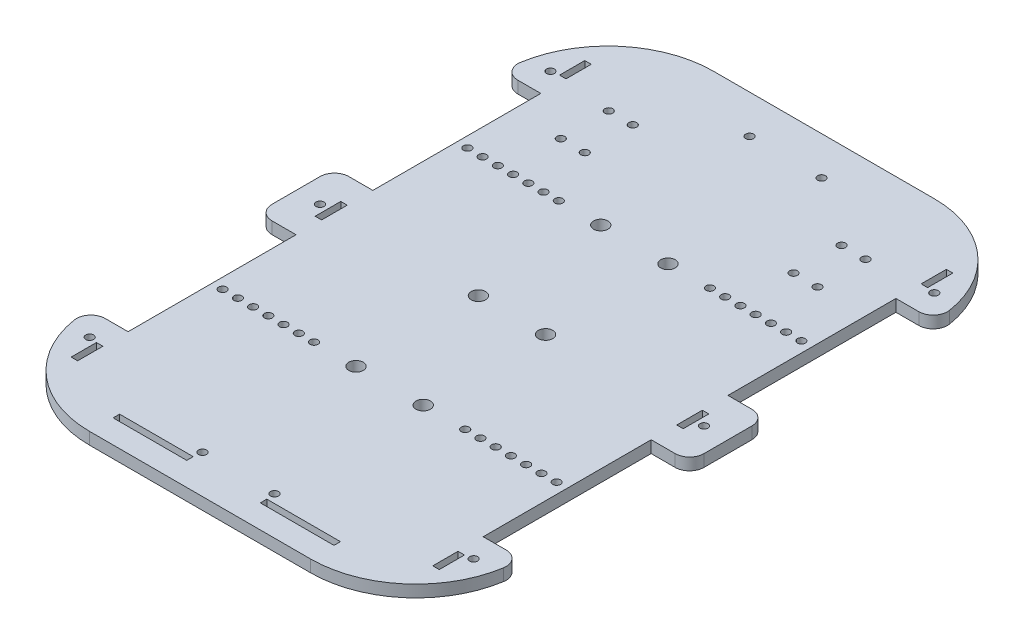
SolidWorks part; units mm, degrees
ref_plane "Ön Düzlem" through (0, 0, 0) normal (0, 0, 1) x (1, 0, 0)
ref_plane "Üst Düzlem" through (0, 0, 0) normal (0, 1, 0) x (1, 0, 0)
ref_plane "Sağ Düzlem" through (0, 0, 0) normal (1, 0, 0) x (0, 0, -1)
sketch "Sketch2" plane through (0, 0, 0) normal (0, 1, 0) x (1, 0, 0)
  line L0 (-74, -86) -> (-74, -51) construction
  line L1 (46, -130) -> (-46, -130)
  line L2 (90, -10) -> (90, 10)
  line L3 (46, 130) -> (-46, 130)
  line L4 (-90, -10) -> (-90, 10)
  line L5 (90, -130) -> (-90, 130) construction
  line L6 (90, 130) -> (-90, -130) construction
  line L7 (-83.5233, 86) -> (-74, 86)
  line L9 (-84, 16) -> (-74, 16)
  line L10 (-74, 86) -> (-74, 16)
  line L11 (-83.5233, -86) -> (-74, -86)
  line L13 (-84, -16) -> (-74, -16)
  line L14 (-74, -86) -> (-74, -16)
  line L15 (83.5233, 86) -> (74, 86)
  line L17 (84, 16) -> (74, 16)
  line L18 (74, 86) -> (74, 16)
  line L19 (83.5233, -86) -> (74, -86)
  line L21 (84, -16) -> (74, -16)
  line L22 (74, -86) -> (74, -16)
  line L23 (-74, 51) -> (74, 51) construction
  line L24 (-74, -51) -> (74, -51) construction
  line L26 (-74, 96.51) -> (-76.7, 96.51)
  line L27 (-76.7, 96.51) -> (-76.7, 107.02)
  line L28 (-74, 107.02) -> (-76.7, 107.02)
  line L29 (-74, 96.51) -> (-74, 107.02)
  line L30 (74, 96.51) -> (74, 107.02)
  line L31 (74, 107.02) -> (76.7, 107.02)
  line L32 (76.7, 96.51) -> (76.7, 107.02)
  line L33 (74, 96.51) -> (76.7, 96.51)
  line L34 (74, -107.02) -> (76.7, -107.02)
  line L35 (76.7, -96.51) -> (76.7, -107.02)
  line L36 (74, -96.51) -> (74, -107.02)
  line L37 (74, -96.51) -> (76.7, -96.51)
  line L38 (-74, -96.51) -> (-74, -107.02)
  line L39 (-74, -107.02) -> (-76.7, -107.02)
  line L40 (-76.7, -96.51) -> (-76.7, -107.02)
  line L41 (-74, -96.51) -> (-76.7, -96.51)
  line L42 (-74, 5.3333) -> (-74, -5.3333)
  line L43 (74, 5.3333) -> (74, -5.3333)
  line L44 (-74, 5.3333) -> (-76.7, 5.3333)
  line L45 (-76.7, 5.3333) -> (-76.7, -5.3333)
  line L46 (-76.7, -5.3333) -> (-74, -5.3333)
  line L47 (74, 5.3333) -> (76.7, 5.3333)
  line L48 (76.7, 5.3333) -> (76.7, -5.3333)
  line L49 (76.7, -5.3333) -> (74, -5.3333)
  line L53 (-46.02, -117.52) -> (-15.34, -117.52)
  line L55 (15.34, -117.52) -> (46.02, -117.52)
  line L56 (-46.02, -117.52) -> (-46.02, -120.22)
  line L57 (-46.02, -120.22) -> (-15.34, -120.22)
  line L58 (46.02, -120.22) -> (46.02, -117.52)
  line L59 (15.34, -117.52) -> (15.34, -120.22)
  line L60 (-15.34, -117.52) -> (-15.34, -120.22)
  line L61 (15.34, -120.22) -> (46.02, -120.22)
  arc A2 (-46, -130) -> (-89.4481, -92.9474) centre (-46, -86) cw
  arc A3 (-89.4481, 92.9474) -> (-46, 130) centre (-46, 86) cw
  arc A4 (89.4481, 92.9474) -> (46, 130) centre (46, 86) ccw
  arc A5 (89.4481, -92.9474) -> (46, -130) centre (46, -86) cw
  arc A6 (-84, 16) -> (-90, 10) centre (-84, 10) ccw
  arc A7 (-84, -16) -> (-90, -10) centre (-84, -10) cw
  arc A8 (90, 10) -> (84, 16) centre (84, 10) ccw
  arc A9 (90, -10) -> (84, -16) centre (84, -10) cw
  arc A10 (-89.4481, -92.9474) -> (-83.5233, -86) centre (-83.5233, -92) cw
  arc A11 (83.5233, -86) -> (89.4481, -92.9474) centre (83.5233, -92) cw
  arc A12 (-89.4481, 92.9474) -> (-83.5233, 86) centre (-83.5233, 92) ccw
  arc A13 (89.4481, 92.9474) -> (83.5233, 86) centre (83.5233, 92) cw
  point P0 (0, 0)
  point P34 (-90, -16)
  point P39 (90, -16)
  point P46 (-90, 86)
  point P49 (90, 86)
  dimension "D3" = 44
  dimension "D4" = 44
  dimension "D5" = 44
  dimension "D6" = 44
  dimension "D15" = 6
  dimension "D16" = 6
  dimension "D17" = 6
  dimension "D18" = 6
  dimension "D19" = 6
  dimension "D20" = 6
  dimension "D21" = 6
  dimension "D22" = 6
  dimension "D1" = 260
  dimension "D2" = 180
  dimension "D7" = 16
  dimension "D8" = 70
  dimension "D9" = 16
  dimension "D10" = 70
  dimension "D11" = 70
  dimension "D12" = 16
  dimension "D13" = 16
  dimension "D14" = 70
extrude "Boss-Extrude4" add sketch "Sketch2" along normal blind 5
sketch "Sketch5" plane through (0, 5, 0) normal (0, 1, 0) x (1, 0, 0)
  line L0 (-53.5, 73.83) -> (-43.5, 73.83) construction
  line L1 (-43.5, 73.83) -> (-43.5, 93.83) construction
  line L2 (-43.5, 93.83) -> (-43.5808, 93.8151) construction
  line L3 (-43.5808, 93.8151) -> (-53.5, 93.83) construction
  line L4 (-74, 86) -> (-74, 16) construction
  line L5 (53.5, 93.83) -> (43.5, 93.83) construction
  line L6 (43.5, 93.83) -> (43.5, 73.83) construction
  line L7 (43.5, 73.83) -> (53.5, 73.83) construction
  line L8 (74, 16) -> (74, 86) construction
  line L9 (46, 130) -> (-46, 130) construction
  circle A0 centre (-69.6, -51) radius 1.65
  circle A1 centre (-63.25, -51) radius 1.65
  circle A2 centre (-56.9, -51) radius 1.65
  circle A3 centre (-50.55, -51) radius 1.65
  circle A4 centre (-44.2, -51) radius 1.65
  circle A5 centre (-37.85, -51) radius 1.65
  circle A6 centre (-31.5, -51) radius 1.65
  circle A7 centre (31.5, -51) radius 1.65
  circle A8 centre (37.85, -51) radius 1.65
  circle A9 centre (44.2, -51) radius 1.65
  circle A10 centre (50.55, -51) radius 1.65
  circle A11 centre (56.9, -51) radius 1.65
  circle A12 centre (63.25, -51) radius 1.65
  circle A13 centre (69.6, -51) radius 1.65
  circle A14 centre (69.6, 51) radius 1.65
  circle A15 centre (63.25, 51) radius 1.65
  circle A16 centre (56.9, 51) radius 1.65
  circle A17 centre (50.55, 51) radius 1.65
  circle A18 centre (44.2, 51) radius 1.65
  circle A19 centre (37.85, 51) radius 1.65
  circle A20 centre (31.5, 51) radius 1.65
  circle A21 centre (-31.5, 51) radius 1.65
  circle A22 centre (-37.85, 51) radius 1.65
  circle A23 centre (-44.2, 51) radius 1.65
  circle A24 centre (-50.55, 51) radius 1.65
  circle A25 centre (-56.9, 51) radius 1.65
  circle A26 centre (-63.25, 51) radius 1.65
  circle A27 centre (-69.6, 51) radius 1.65
  circle A29 centre (-14, -51) radius 3
  circle A30 centre (14, -51) radius 3
  circle A31 centre (14, 51) radius 3
  circle A32 centre (-14, 51) radius 3
  circle A33 centre (-14, 0) radius 3
  circle A34 centre (14, 0) radius 3
  circle A35 centre (-80, 96) radius 1.65
  circle A36 centre (-80, 0) radius 1.65
  circle A37 centre (80, 0) radius 1.65
  circle A38 centre (-80, -96) radius 1.65
  circle A39 centre (80, -96) radius 1.65
  circle A40 centre (80, 96) radius 1.65
  circle A41 centre (-15, -114) radius 1.65
  circle A42 centre (15, -114) radius 1.65
  circle A43 centre (15, 114) radius 1.65
  circle A44 centre (-15, 114) radius 1.65
  circle A45 centre (-53.5, 93.83) radius 1.65
  circle A46 centre (-53.5, 73.83) radius 1.65
  circle A47 centre (-43.5, 73.83) radius 1.65
  circle A48 centre (-43.5, 93.83) radius 1.65
  circle A49 centre (43.5, 73.83) radius 1.65
  circle A50 centre (53.5, 73.83) radius 1.65
  circle A51 centre (43.5, 93.83) radius 1.65
  circle A52 centre (53.5, 93.83) radius 1.65
  dimension "D1" = 20.5
  dimension "D2" = 20.5
  dimension "D3" = 36.17
  dimension "D4" = 56.17
  dimension "D5" = 56.17
extrude "Cut-Extrude1" cut sketch "Sketch5" against normal through all
